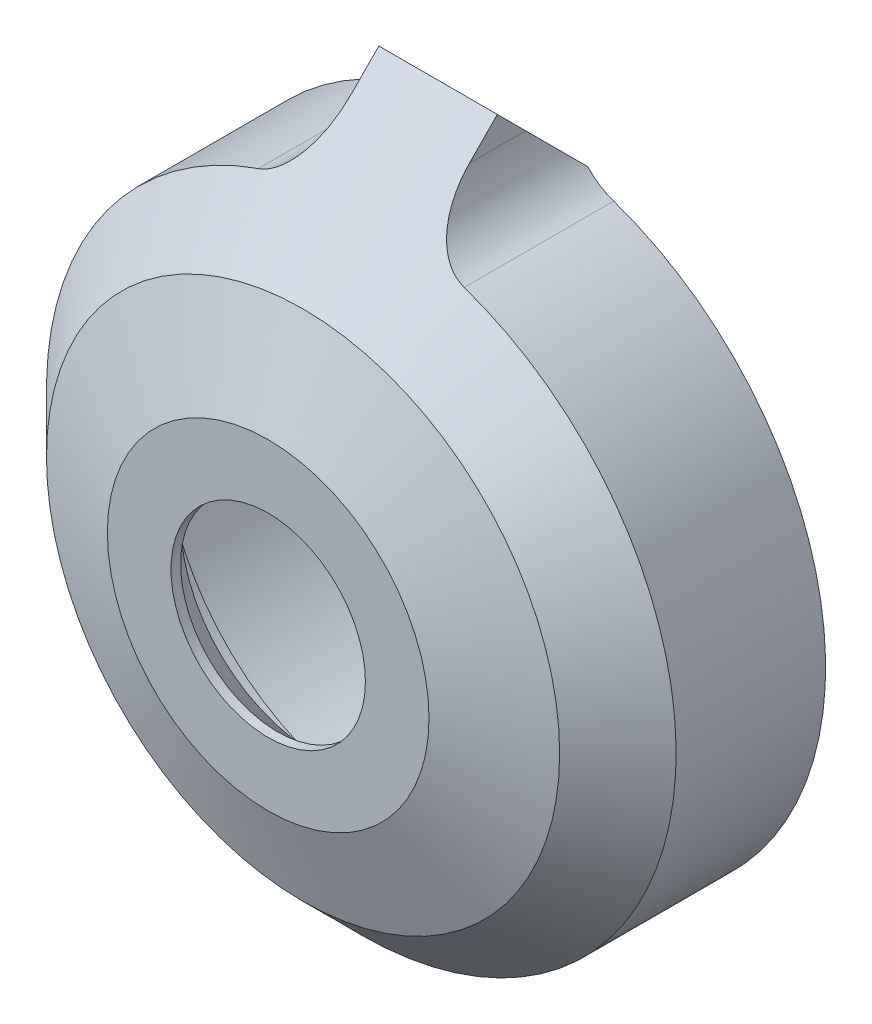
SolidWorks part; units mm, degrees
ref_plane "Front Plane" through (0, 0, 0) normal (0, 0, 1) x (1, 0, 0)
ref_plane "Top Plane" through (0, 0, 0) normal (0, 1, 0) x (1, 0, 0)
ref_plane "Right Plane" through (0, 0, 0) normal (1, 0, 0) x (0, 0, -1)
sketch "Sketch1" plane through (0, 0, 0) normal (1, 0, 0) x (0, 0, -1)
  line L0 (0, 0) -> (19.2462, 0) construction
  line L1 (0, 0) -> (0, 21.2473) construction
  line L2 (0.15, 5.25) -> (0.15, 8.6843)
  line L3 (0.15, 8.6843) -> (3.1767, 17)
  line L4 (3.1767, 17) -> (13.25, 17)
  line L5 (13.25, 17) -> (13.25, 13.05)
  line L6 (13.25, 13.05) -> (6.45, 13.05)
  line L7 (6.45, 13.05) -> (6.45, 11.95)
  line L8 (6.45, 11.95) -> (2.65, 11.95)
  line L9 (2.65, 11.95) -> (2.65, 7.2305)
  line L10 (2.65, 7.2305) -> (0.6695, 5.25)
  line L11 (0.6695, 5.25) -> (0.15, 5.25)
  dimension "D1" = 5.25
  dimension "D2" = 17
  dimension "D3" = 13.05
  dimension "D4" = 11.95
  dimension "D5" = 13.1
  dimension "D6" = 0.3
  dimension "D7" = 2.5
  dimension "D8" = 135
  dimension "D9" = 200
  dimension "D10" = 6.8
revolve "Revolve1" add sketch "Sketch1" angle 360 about L0
chamfer "Chamfer1" distance 2 angle 45 1 edges at (17, 0, -3.1767) first distance on face at (17, 0, -3.1767)
sketch "Sketch2" plane through (0, 0, -13.25) normal (0, 0, -1) x (-1, 0, 0)
  line L0 (0, 0) -> (0, 28.005) construction
  line L1 (3.2, 16.6961) -> (3.2, 23.9782)
  line L2 (-3.2, 16.6961) -> (-3.2, 23.9782)
  line L3 (-3.2, 23.9782) -> (3.2, 23.9782)
  line L4 (-3.2, 0) -> (-3.2, 28.005) construction
  line L5 (3.2, 0) -> (3.2, 28.005) construction
  arc A0 (-3.2, 16.6961) -> (3.2, 16.6961) centre (0, 0) cw
  circle A1 centre (0, 0) radius 17 construction
  dimension "D1" = 3.2
  dimension "D2" = 3.2
extrude "Boss-Extrude1" add sketch "Sketch2" against normal up to surface (0.8825 mm away) up to face at (-17, 0, -5.1767)
chamfer "Chamfer2" distance 7 angle 45 1 edges at (0, 23.9782, -13.25)
sketch "Sketch3" plane through (0, 15.1141, -15.1141) normal (0, 0.7071, -0.7071) x (-1, 0, 0)
  line L0 (0, 2.6362) -> (0, 8.3604) construction
  line L1 (3.2, 2.6362) -> (-3.2, 2.6362) construction
  line L2 (-3.2, 5.4862) -> (3.2, 5.4862) construction
  line L3 (-3.2, 2.6362) -> (-3.2, 8.1882) construction
  line L4 (3.2, 8.1882) -> (3.2, 2.6362) construction
  line L6 (0, 8.3604) -> (3.7232, 8.3604) construction
  ellipse E0 centre (0, -1.437) end of major axis (13.8555, -1.437) minor radius 9.7973 construction
  dimension "D1" = 2.85
hole_wizard "Ø1.6 (1.6) Diameter Hole1" positions "Sketch4" profile "Sketch5" hole size "Ø1.6" standard "DIN" end condition up to next
sketch "Sketch4" plane through (0, 15.1141, -15.1141) normal (0, 0.7071, -0.7071) x (-1, 0, 0)
  line L0 (3.2, 2.6362) -> (-3.2, 2.6362) construction
  point P0 (0, 5.4862)
  dimension "D1" = 2.85
sketch "Sketch5" plane through (0, 18.9935, -11.2347) normal (1, 0, 0) x (0, 0.7071, 0.7071)
  line L0 (0, 0) -> (0, 9.961)
  line L1 (0, 9.961) -> (0.8, 9.961)
  line L2 (0.8, 9.961) -> (0.8, 0)
  line L5 (0.8, 0) -> (0, 0)
  line L11 (0, -6.35) -> (0, 107.95) construction
  dimension "Thru Hole Dia." = 1.6
  dimension "Thru Hole Depth" = 9.961
fillet "Fillet1" radius 3.5 2 edges at (-3.2, 16.6961, -9.2133) (3.2, 16.6961, -9.2133)
hole_wizard "Ø2.0mm Dowel Hole1" positions "Sketch6" profile "Sketch7" hole size "Ø2.0" standard "DIN"
sketch "Sketch6" plane through (0, 0, -13.25) normal (0, 0, -1) x (-1, 0, 0)
  circle A0 centre (0, 0) radius 5.25 construction
  point P0 (0, -15)
  dimension "D1" = 15
sketch "Sketch7" plane through (0, -15, -13.25) normal (1, 0, 0) x (0, 1, 0)
  line L0 (0, 0) -> (0, 9)
  line L1 (0, 9) -> (1, 8.3991)
  line L2 (1, 8.3991) -> (1, 0)
  line L5 (1, 0) -> (0, 0)
  line L10 (0, 9) -> (-1, 8.3991) construction
  line L11 (0, -6.35) -> (0, 107.95) construction
  dimension "Hole Dia." = 2
  dimension "Hole Depth" = 9
  dimension "Drill Angle" = 118
